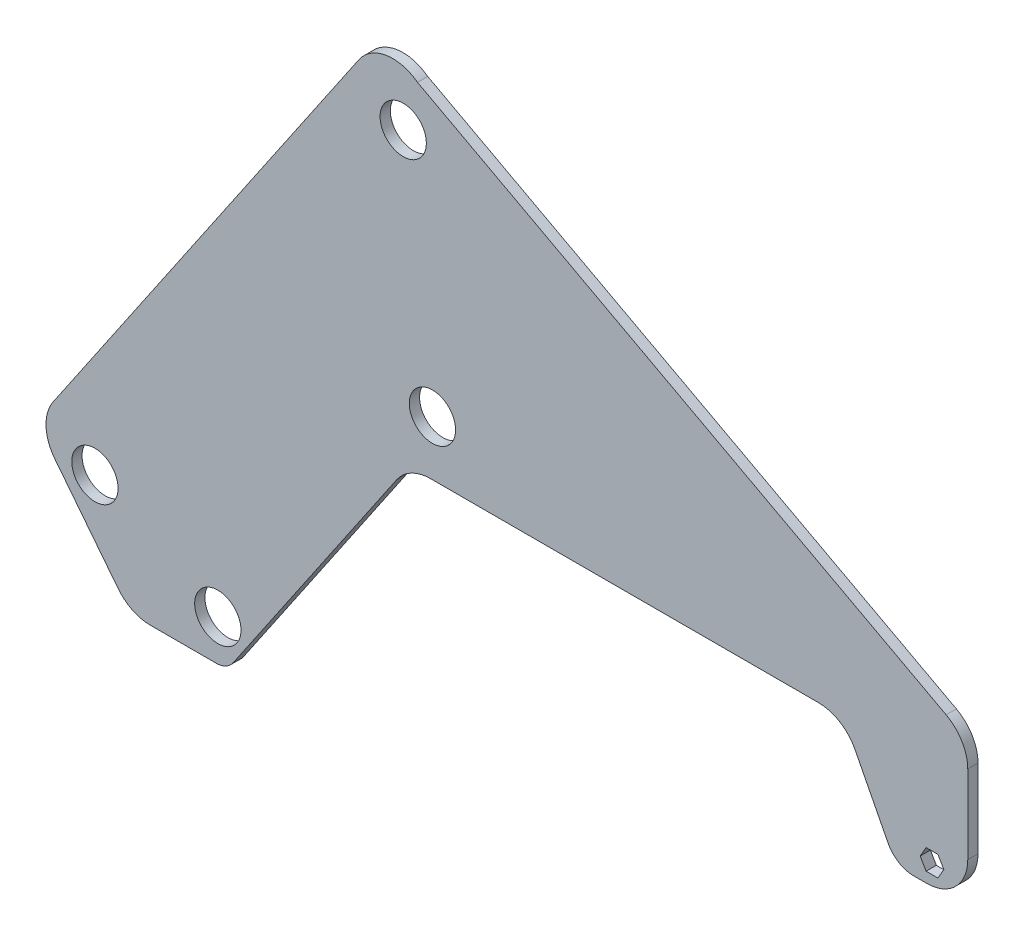
SolidWorks part; units mm, degrees
other "Markup1"
sketch "Sketch1" plane through (-441.7893, 331.8239, 6.35) normal (-0.0431, 0.0102, 0.999) x (0.9985, 0.0354, 0.0427)
sketch "Sketch2" plane through (-413.6701, 343.933, 6.35) normal (-0.0431, 0.0102, 0.999) x (0.9985, 0.0354, 0.0427)
sketch "Sketch3" plane through (-436.3774, 318.5567, 6.35) normal (-0.0431, 0.0102, 0.999) x (0.9985, 0.0354, 0.0427)
sketch "Sketch5" plane through (-436.3774, 318.5567, 6.35) normal (-0.0431, 0.0102, 0.999) x (0.9985, 0.0354, 0.0427)
other "Markup2"
sketch "Sketch4" plane through (102.4721, 318.5567, 6.35) normal (0.9364, 0.1073, 0.3342) x (0.3416, -0.0598, -0.9379)
sketch "Sketch6" plane through (102.4721, 318.5567, 6.35) normal (0.9364, 0.1073, 0.3342) x (0.3416, -0.0598, -0.9379)
ref_plane "Front Plane" through (0, 0, 0) normal (0, 0, 1) x (1, 0, 0)
ref_plane "Top Plane" through (0, 0, 0) normal (0, 1, 0) x (1, 0, 0)
ref_plane "Right Plane" through (0, 0, 0) normal (1, 0, 0) x (0, 0, -1)
sketch "Model" plane through (0, 0, 0) normal (0, 0, 1) x (1, 0, 0)
  line L1 (-191.9011, 104.6502) -> (-2.1388, 104.6502)
  line L3 (-314.2383, -55.3595) -> (-212.8994, 93.5413)
  line L4 (-236.3032, 307.4477) -> (-425.9209, 28.8361)
  line L5 (-424.8981, -1.1437) -> (-385.5815, -51.2028)
  line L13 (126.3831, 53.8502) -> (122.717, 60.2002)
  line L14 (122.717, 60.2002) -> (115.3846, 60.2002)
  line L15 (115.3846, 60.2002) -> (111.7185, 53.8502)
  line L16 (111.7185, 53.8502) -> (115.3846, 47.5002)
  line L17 (115.3846, 47.5002) -> (122.717, 47.5002)
  line L18 (122.717, 47.5002) -> (126.3831, 53.8502)
  line L19 (-365.606, -60.914) -> (-324.7375, -60.914)
  line L20 (-871.0211, -88.854) -> (370.1019, -88.854) construction
  line L22 (141.2086, 66.5502) -> (141.2086, 78.8846)
  line L27 (107.6196, 41.1502) -> (115.8086, 41.1502)
  line L28 (-399.9752, 2.586) -> (-323.7752, -35.514) construction
  line L29 (-323.7752, -35.514) -> (-190.7071, 138.5169) construction
  line L30 (-190.7071, 138.5169) -> (-208.8329, 283.4378) construction
  line L31 (-208.8329, 283.4378) -> (-399.9752, 2.586) construction
  line L32 (91.8004, 50.8135) -> (71.26, 90.8456)
  line L33 (48.6612, 104.6502) -> (-11.3966, 104.6502)
  line L34 (141.2086, 78.8846) -> (141.2086, 115.3033)
  line L35 (127.8091, 137.6897) -> (-199.9496, 313.3896)
  arc A3 (121.2475, 59.8082) -> (121.352, 60.2002) centre (96.7586, 66.5502) ccw
  circle A9 centre (-323.7752, -35.514) radius 14.351
  circle A10 centre (-399.9752, 2.586) radius 14.351
  circle A12 centre (-190.7071, 138.5169) radius 14.351
  arc A15 (107.6196, 41.1502) -> (91.8004, 50.8135) centre (107.6196, 58.9302) cw
  arc A21 (-191.9011, 104.6502) -> (-212.8994, 93.5413) centre (-191.9011, 79.2502) ccw
  circle A22 centre (-208.8329, 283.4378) radius 14.351
  circle A24 centre (119.0508, 53.8502) radius 6.35 construction
  arc A31 (-324.7375, -60.914) -> (-314.2383, -55.3595) centre (-324.7375, -48.214) ccw
  arc A40 (114.7422, 48.6129) -> (115.0458, 48.9225) centre (96.7586, 66.5502) ccw
  arc A43 (115.8086, 41.1502) -> (141.2086, 66.5502) centre (115.8086, 66.5502) ccw
  arc A44 (-236.3032, 307.4477) -> (-199.9496, 313.3896) centre (-215.305, 293.1567) cw
  arc A45 (-365.606, -60.914) -> (-385.5815, -51.2028) centre (-365.606, -35.514) cw
  arc A46 (71.26, 90.8456) -> (48.6612, 104.6502) centre (48.6612, 79.2502) ccw
  arc A47 (141.2086, 115.3033) -> (127.8091, 137.6897) centre (115.8086, 115.3033) ccw
  arc A48 (-424.8981, -1.1437) -> (-425.9209, 28.8361) centre (-404.9226, 14.5451) cw
  ellipse E0 centre (-551.1692, 173.9527) end of major axis (-591.2054, 216.0961) minor radius 17.278
  point P31 (-177.5612, 330.9695)
  point P34 (100.2935, -12.8222)
  point P43 (-377.9543, -60.914)
  point P55 (96.7586, 41.1502)
  point P59 (174.831, 53.8502)
  point P60 (-205.3388, 104.6502)
  point P64 (-436.3774, 13.472)
  dimension "D3" = 38.1
  dimension "D4" = 104.6502
  dimension "D5" = 76.2
  dimension "D6" = 44.45
  dimension "D7" = 12.7
  dimension "D8" = 28.702
  dimension "D11" = 139.7
  dimension "D12" = 27.94
  dimension "D21" = 124.238
  dimension "D13" = 12.7
  dimension "D16" = 355.6
  dimension "D23" = 25.4
  dimension "D24" = 25.4
  dimension "D26" = 25.4
  dimension "D14" = 406.4
  dimension "D20" = 254
  dimension "D29" = 25.4
  dimension "D31" = 25.4
  dimension "D25" = 88.9
  dimension "D30" = 17.78
  dimension "D32" = 25.4
  dimension "D33" = 25.4
  dimension "D9" = 19.05
  dimension "D10" = 146.05
  dimension "D15" = 33.8667
  dimension "D17" = 339.725
  dimension "D18" = 219.075
  dimension "D19" = 50.8
  dimension "D22" = 25.4
  dimension "D27" = 53.2168
  dimension "D28" = 12.7
extrude "Boss-Extrude1" add sketch "Model" along normal blind 6.35 contours L5 L3 L1 L4 A22 A9 A10 A12 region at (-206.9871, 107.7659, 0)
